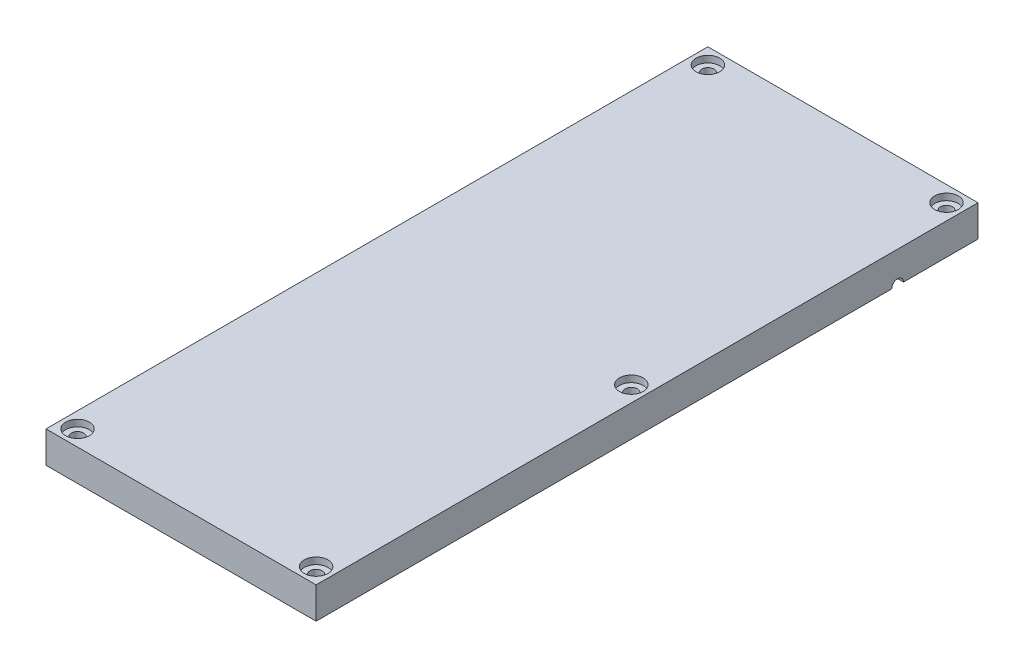
SolidWorks part; units mm, degrees
ref_plane "Front Plane" through (0, 0, 0) normal (0, 0, 1) x (1, 0, 0)
ref_plane "Top Plane" through (0, 0, 0) normal (0, 1, 0) x (1, 0, 0)
ref_plane "Right Plane" through (0, 0, 0) normal (1, 0, 0) x (0, 0, -1)
sketch "Sketch1" plane through (0, 0, 0) normal (0, 1, 0) x (1, 0, 0)
  line L1 (37.211, 0) -> (146.05, 0)
  line L2 (37.211, 0) -> (37.211, 266.7)
  line L3 (37.211, 266.7) -> (146.05, 266.7)
  line L4 (146.05, 0) -> (146.05, 266.7)
  dimension "D1" = 266.7
  dimension "D2" = 108.839
  dimension "D3" = 146.05
  dimension "D4" = 266.7
extrude "Boss-Extrude1" add sketch "Sketch1" along normal blind 12.7 from offset 12.7
hole_wizard "CBORE for #8 Binding Head Machine Screw1" positions "Sketch3" profile "Sketch2" counterbore size "#8" standard "ANSI Inch" end condition through all
sketch "Sketch3" plane through (0, 25.4, 0) normal (0, 1, 0) x (1, 0, 0)
  line L0 (146.05, 0) -> (146.05, 266.7) construction
  line L1 (37.211, 0) -> (146.05, 0) construction
  line L2 (146.05, 266.7) -> (37.211, 266.7) construction
  line L3 (37.211, 266.7) -> (37.211, 0) construction
  point P0 (139.7, 6.35)
  point P2 (139.7, 260.35)
  point P13 (43.561, 6.35)
  point P15 (43.561, 260.35)
  point P20 (139.7, 133.35)
  dimension "D1" = 6.35
  dimension "D2" = 6.35
  dimension "D3" = 6.35
  dimension "D4" = 6.35
  dimension "D5" = 6.35
  dimension "D6" = 6.35
  dimension "D7" = 6.35
  dimension "D8" = 6.35
  dimension "D9" = 6.35
  dimension "D10" = 133.35
sketch "Sketch2" plane through (139.7, 25.4, -6.35) normal (1, 0, 0) x (0, 0, 1)
  line L0 (0, 0) -> (0, 12.7)
  line L1 (0, 12.7) -> (2.4574, 12.7)
  line L3 (2.4574, 12.7) -> (2.4575, 2.667)
  line L4 (2.4575, 2.667) -> (4.7625, 2.667)
  line L5 (4.7625, 2.667) -> (4.7625, 0)
  line L7 (4.7625, 0) -> (0, 0)
  line L11 (0, -6.35) -> (0, 107.95) construction
  dimension "Thru Hole Dia." = 4.9149
  dimension "Thru Hole Depth" = 12.7
  dimension "C'Bore Dia." = 9.525
  dimension "C'Bore Depth" = 2.667
sketch "Sketch4" plane through (0, 12.7, 0) normal (0, -1, 0) x (-1, 0, 0)
  line L0 (-37.211, 266.7) -> (-37.211, 0) construction
  line L1 (-43.561, 18.415) -> (-114.935, 18.415)
  line L2 (-43.561, 18.415) -> (-43.561, 241.935)
  line L3 (-43.561, 241.935) -> (-114.935, 241.935)
  line L4 (-114.935, 18.415) -> (-114.935, 241.935)
  line L5 (-37.211, 0) -> (-146.05, 0) construction
  line L6 (-146.05, 266.7) -> (-37.211, 266.7) construction
  line L7 (-146.05, 0) -> (-146.05, 266.7) construction
  dimension "D1" = 6.35
  dimension "D2" = 18.415
  dimension "D3" = 24.765
  dimension "D4" = 31.115
extrude "Cut-Extrude1" cut sketch "Sketch4" against normal blind 9.525
sketch "Sketch5" plane through (0, 12.7, 0) normal (0, -1, 0) x (1, 0, 0)
  line L0 (114.935, -196.215) -> (120.015, -196.215)
  line L1 (114.935, -241.935) -> (114.935, -18.415) construction
  line L2 (120.015, -196.215) -> (120.015, -234.315)
  line L3 (120.015, -234.315) -> (128.905, -234.315)
  line L4 (128.905, -234.315) -> (128.905, -158.115)
  line L5 (128.905, -158.115) -> (137.795, -158.115)
  line L6 (137.795, -158.115) -> (137.795, -234.315)
  line L7 (137.795, -234.315) -> (146.05, -234.315)
  line L8 (146.05, 0) -> (146.05, -266.7) construction
  line L9 (114.935, -18.415) -> (43.561, -18.415) construction
  dimension "D1" = 38.1
  dimension "D2" = 76.2
  dimension "D3" = 76.2
  dimension "D4" = 5.08
  dimension "D5" = 8.89
  dimension "D6" = 8.89
  dimension "D7" = 177.8
sketch "Sketch6" plane through (146.05, 0, 0) normal (1, 0, 0) x (0, 0, -1)
  line L0 (234.315, 12.7) -> (158.115, 12.7) construction
  line L1 (196.215, 12.7) -> (234.315, 12.7) construction
  circle A0 centre (234.315, 12.7) radius 2.3813
  dimension "D1" = 4.7625
  dimension "D2" = 0
sweep "Cut-Sweep1" cut profiles "Sketch6" path "Sketch5"
sketch "Sketch8" plane through (0, 12.7, 0) normal (0, -1, 0) x (1, 0, 0)
  line L0 (114.935, -193.8337) -> (114.935, -18.415) construction
  line L1 (114.935, -18.415) -> (127.635, -18.415)
  line L2 (114.935, -18.415) -> (114.935, -31.115)
  line L3 (114.935, -31.115) -> (127.635, -31.115)
  line L4 (127.635, -18.415) -> (127.635, -31.115)
  line L5 (43.561, -241.935) -> (114.935, -241.935) construction
  line L6 (102.235, -241.935) -> (114.935, -241.935)
  line L7 (102.235, -241.935) -> (102.235, -254.635)
  line L8 (102.235, -254.635) -> (114.935, -254.635)
  line L9 (114.935, -241.935) -> (114.935, -254.635)
  line L10 (114.935, -241.935) -> (114.935, -18.415) construction
  line L11 (114.935, -18.415) -> (43.561, -18.415) construction
  dimension "D1" = 12.7
  dimension "D2" = 12.7
  dimension "D3" = 12.7
  dimension "D4" = 12.7
  dimension "D5" = 0
  dimension "D6" = 0
extrude "Cut-Extrude3" cut sketch "Sketch8" against normal blind 9.525
